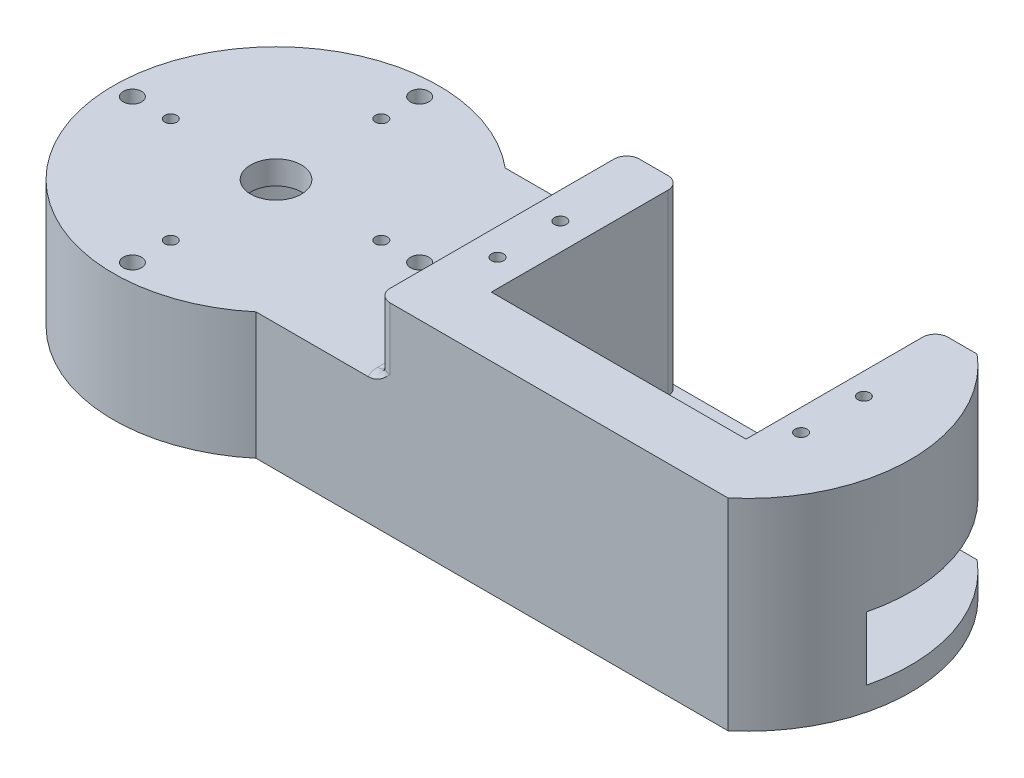
SolidWorks part; units mm, degrees
ref_plane "Front Plane" through (0, 0, 0) normal (0, 0, 1) x (1, 0, 0)
ref_plane "Top Plane" through (0, 0, 0) normal (0, 1, 0) x (1, 0, 0)
ref_plane "Right Plane" through (0, 0, 0) normal (1, 0, 0) x (0, 0, -1)
sketch "Sketch1" plane through (0, 0, 0) normal (0, 1, 0) x (1, 0, 0)
  line L0 (25.65, 0) -> (44.15, 0) construction
  line L1 (44.15, -10.195) -> (84.31, -10.195)
  line L2 (44.15, 10.195) -> (84.31, 10.195)
  line L3 (44.15, 10.195) -> (44.15, -10.195)
  line L4 (44.15, 0) -> (84.31, 0) construction
  line L5 (84.31, 10.195) -> (84.31, -10.195)
  line L6 (92.81, 17.8861) -> (92.81, -17.8861)
  line L7 (35.65, -18.695) -> (91.9869, -18.695)
  line L8 (35.65, 18.695) -> (35.65, -18.695)
  line L9 (35.65, 18.695) -> (91.9869, 18.695)
  line L10 (0, 25.65) -> (74.425, 25.65)
  line L11 (0, -25.65) -> (74.425, -25.65)
  line L12 (35.65, 18.695) -> (92.81, 18.695) construction
  line L13 (92.81, 18.695) -> (92.81, -18.695) construction
  line L14 (35.65, -18.695) -> (92.81, -18.695) construction
  circle A0 centre (0, 0) radius 15.65 construction
  circle A1 centre (16.6, 0) radius 0.95
  circle A2 centre (0, -16.6) radius 0.95
  circle A3 centre (-16.6, 0) radius 0.95
  circle A4 centre (0, 16.6) radius 0.95
  circle A5 centre (0, 0) radius 19.65
  circle A6 centre (0, 0) radius 4
  circle A7 centre (0, 0) radius 25.65
  circle A8 centre (74.425, 0) radius 25.65 construction
  arc A9 (74.425, 25.65) -> (74.425, -25.65) centre (74.425, 0) cw
  arc A10 (0, -25.65) -> (0, 25.65) centre (0, 0) cw
  point P14 (0, 0)
  point P28 (64.23, 0)
  point P29 (74.425, 0)
  dimension "D1" = 31.3
  dimension "D2" = 1.9
  dimension "D5" = 8
  dimension "D7" = 10
  dimension "D8" = 40.16
  dimension "D9" = 20.39
  dimension "D11" = 10.195
  dimension "D4" = 4
  dimension "D6" = 6
  dimension "D10" = 8.5
  dimension "D3" = 4
extrude "Boss-Extrude2" add sketch "Sketch1" along normal blind 3.7 contours A7 A5 | A5 A6 A1 A2 A3 A4 | A9 L10 A7 L11 L7 L8 L9 | A9 L9 L8 L7 L6 L2 L5 L1 L3 | L5 L2 L3 L1 | A9 L6 region at (64.23, 0, 0) region at (95.7544, 0, 0) region at (92.127, 0, 0) region at (63.8184, 0, -19.7482) region at (17.6243, 0, -17.6243) region at (-19.0942, 0, 0)
sketch "Sketch5" plane through (0, 3.7, 0) normal (0, 1, 0) x (1, 0, 0)
  line L0 (35.65, -18.695) -> (91.9869, -18.695) construction
  line L1 (35.65, 18.695) -> (35.65, -18.695) construction
  line L2 (74.425, 25.65) -> (0, 25.65)
  line L3 (0, -25.65) -> (74.425, -25.65)
  line L4 (44.15, -10.195) -> (84.31, -10.195)
  line L5 (84.31, -10.195) -> (84.31, 10.195)
  line L6 (84.31, 10.195) -> (44.15, 10.195)
  line L7 (44.15, 10.195) -> (44.15, -10.195)
  line L8 (44.15, -10.195) -> (84.31, -10.195)
  line L9 (84.31, -10.195) -> (84.31, 10.195)
  line L10 (84.31, 10.195) -> (44.15, 10.195)
  line L11 (44.15, 10.195) -> (44.15, -10.195)
  line L12 (74.425, 25.65) -> (0, 25.65)
  line L13 (0, -25.65) -> (74.425, -25.65)
  line L14 (35.65, 18.695) -> (91.9869, 18.695) construction
  line L15 (92.81, 17.8861) -> (92.81, -17.8861) construction
  line L16 (35.65, -18.695) -> (91.9869, -18.695)
  line L17 (35.65, 18.695) -> (35.65, -18.695)
  line L18 (35.65, 18.695) -> (91.9869, 18.695)
  line L19 (92.81, 17.8861) -> (92.81, -17.8861)
  circle A1 centre (0, 0) radius 4
  circle A2 centre (0, 0) radius 4
  circle A3 centre (0, 0) radius 19.65
  circle A4 centre (0, 0) radius 19.65
  circle A5 centre (0, 16.6) radius 0.95
  circle A6 centre (0, 16.6) radius 0.95
  circle A7 centre (-16.6, 0) radius 0.95
  circle A8 centre (-16.6, 0) radius 0.95
  circle A9 centre (0, -16.6) radius 0.95
  circle A10 centre (0, -16.6) radius 0.95
  circle A11 centre (16.6, 0) radius 0.95
  circle A12 centre (16.6, 0) radius 0.95
  circle A13 centre (0, 0) radius 25.65
  circle A14 centre (0, 0) radius 25.65
  arc A16 (74.425, -25.65) -> (74.425, 25.65) centre (74.425, 0) ccw
  arc A17 (0, 25.65) -> (0, -25.65) centre (0, 0) ccw
  arc A18 (74.425, -25.65) -> (74.425, 25.65) centre (74.425, 0) ccw
  arc A19 (0, 25.65) -> (0, -25.65) centre (0, 0) ccw
  arc M16 (74.425, -25.65) -> (74.425, 25.65) centre (74.425, 0) ccw
  line M17 (74.425, 25.65) -> (0, 25.65)
  arc M18 (0, 25.65) -> (0, -25.65) centre (0, 0) ccw
  line M19 (0, -25.65) -> (74.425, -25.65)
  dimension "D1" = 0
  dimension "D2" = 0
  dimension "D3" = 0
  dimension "D4" = 0
  dimension "D5" = 0
  dimension "D6" = 0
  dimension "D7" = 0
  dimension "D8" = 0
  dimension "D9" = 0
extrude "Boss-Extrude3" add sketch "Sketch5" along normal blind 28.1 contours A14 A4 M18 | L19 L18 L17 L16 L11 L10 L9 L8 M16 | A14 L16 L17 L18 M19 M16 M17 | L19 M16 region at (83.4817, 3.7, -22.8687) region at (17.6243, 3.7, -17.6243) region at (91.9243, 3.7, -17.808) region at (95.7544, 3.7, 0)
sketch "Sketch6" plane through (0, 0, -10.195) normal (0, 0, 1) x (1, 0, 0)
  line L1 (44.15, 31.8) -> (84.31, 31.8)
  line L2 (44.15, 31.8) -> (44.15, 3.7)
  line L3 (44.15, 3.7) -> (84.31, 3.7)
  line L4 (84.31, 31.8) -> (84.31, 3.7)
extrude "Cut-Extrude1" cut sketch "Sketch6" against normal up to next
sketch "Sketch7" plane through (84.31, 0, 0) normal (-1, 0, 0) x (0, 0, 1)
  line L0 (10.195, 3.7) -> (-23.6687, 3.7) construction
  line L1 (-23.6687, 3.7) -> (-23.6687, 31.8) construction
  line L2 (6.195, 3.7) -> (-23.6687, 3.7)
  line L3 (6.195, 3.7) -> (6.195, 13.7)
  line L4 (6.195, 13.7) -> (-23.6687, 13.7)
  line L5 (-23.6687, 3.7) -> (-23.6687, 13.7)
  point P0 (6.195, 3.7)
  dimension "D1" = 4
  dimension "D2" = 10
extrude "Cut-Extrude2" cut sketch "Sketch7" against normal up to next
sketch "Sketch8" plane through (0, 31.8, 0) normal (0, 1, 0) x (1, 0, 0)
  line L0 (35.65, -18.695) -> (91.9869, -18.695) construction
  line L1 (35.65, 18.695) -> (35.65, -18.695) construction
  line L2 (74.425, 25.65) -> (0, 25.65)
  line L3 (0, -25.65) -> (74.425, -25.65)
  line L4 (44.15, -10.195) -> (84.31, -10.195)
  line L5 (84.31, -10.195) -> (84.31, 10.195)
  line L6 (84.31, 10.195) -> (44.15, 10.195)
  line L7 (44.15, 10.195) -> (44.15, -10.195)
  line L8 (44.15, -10.195) -> (84.31, -10.195)
  line L9 (84.31, -10.195) -> (84.31, 10.195)
  line L10 (84.31, 10.195) -> (44.15, 10.195)
  line L11 (44.15, 10.195) -> (44.15, -10.195)
  line L12 (74.425, 25.65) -> (0, 25.65)
  line L13 (0, -25.65) -> (74.425, -25.65)
  line L14 (35.65, 18.695) -> (91.9869, 18.695) construction
  line L15 (92.81, 17.8861) -> (92.81, -17.8861) construction
  line L16 (35.65, -18.695) -> (91.9869, -18.695)
  line L17 (35.65, 18.695) -> (35.65, -18.695)
  line L18 (35.65, 18.695) -> (91.9869, 18.695)
  line L19 (92.81, 17.8861) -> (92.81, -17.8861)
  line L20 (19.65, 0) -> (25.65, 0) construction
  circle A0 centre (22.65, 0) radius 1.45
  circle A1 centre (0, 0) radius 4
  circle A2 centre (0, 0) radius 4
  circle A3 centre (0, 0) radius 19.65
  circle A4 centre (0, 0) radius 19.65
  circle A5 centre (0, 16.6) radius 0.95
  circle A6 centre (0, 16.6) radius 0.95
  circle A7 centre (-16.6, 0) radius 0.95
  circle A8 centre (-16.6, 0) radius 0.95
  circle A9 centre (0, -16.6) radius 0.95
  circle A10 centre (0, -16.6) radius 0.95
  circle A11 centre (16.6, 0) radius 0.95
  circle A12 centre (16.6, 0) radius 0.95
  circle A13 centre (0, 0) radius 25.65
  circle A14 centre (0, 0) radius 25.65
  circle A15 centre (0, -22.65) radius 1.45
  arc A16 (74.425, -25.65) -> (74.425, 25.65) centre (74.425, 0) ccw
  arc A17 (0, 25.65) -> (0, -25.65) centre (0, 0) ccw
  arc A18 (74.425, -25.65) -> (74.425, 25.65) centre (74.425, 0) ccw
  arc A19 (0, 25.65) -> (0, -25.65) centre (0, 0) ccw
  circle A20 centre (-22.65, 0) radius 1.45
  circle A21 centre (0, 22.65) radius 1.45
  point P50 (0, 0)
  dimension "D10" = 2.9
  dimension "D1" = 0
  dimension "D2" = 0
  dimension "D3" = 0
  dimension "D4" = 0
  dimension "D5" = 0
  dimension "D6" = 0
  dimension "D7" = 0
  dimension "D8" = 0
  dimension "D9" = 0
  dimension "D11" = 4
extrude "Cut-Extrude3" cut sketch "Sketch8" against normal through all both and the other way through all contours A20 | A21 | A0 | A15
sketch "Sketch9" plane through (0, 31.8, 0) normal (0, 1, 0) x (1, 0, 0)
  line L0 (35.65, -18.695) -> (91.9869, -18.695) construction
  line L1 (35.65, 18.695) -> (35.65, -18.695) construction
  line L2 (74.425, 25.65) -> (0, 25.65)
  line L3 (0, -25.65) -> (74.425, -25.65)
  line L4 (44.15, -10.195) -> (84.31, -10.195)
  line L5 (84.31, -10.195) -> (84.31, 10.195)
  line L6 (84.31, 10.195) -> (44.15, 10.195)
  line L7 (44.15, 10.195) -> (44.15, -10.195)
  line L8 (44.15, -10.195) -> (84.31, -10.195)
  line L9 (84.31, -10.195) -> (84.31, 10.195)
  line L10 (84.31, 10.195) -> (44.15, 10.195)
  line L11 (44.15, 10.195) -> (44.15, -10.195)
  line L12 (74.425, 25.65) -> (0, 25.65)
  line L13 (0, -25.65) -> (74.425, -25.65)
  line L14 (35.65, 18.695) -> (91.9869, 18.695) construction
  line L15 (92.81, 17.8861) -> (92.81, -17.8861) construction
  line L16 (35.65, -18.695) -> (91.9869, -18.695)
  line L17 (35.65, 18.695) -> (35.65, -18.695)
  line L18 (35.65, 18.695) -> (91.9869, 18.695)
  line L19 (92.81, 17.8861) -> (92.81, -17.8861)
  line L20 (35.65, 0) -> (92.81, 0) construction
  line L21 (63.8184, 18.695) -> (63.8184, -18.695) construction
  circle A0 centre (39.88, -4.95) radius 0.95
  circle A1 centre (0, 0) radius 4
  circle A2 centre (0, 0) radius 4
  circle A3 centre (0, 0) radius 19.65
  circle A4 centre (0, 0) radius 19.65
  circle A5 centre (0, 16.6) radius 0.95
  circle A6 centre (0, 16.6) radius 0.95
  circle A7 centre (-16.6, 0) radius 0.95
  circle A8 centre (-16.6, 0) radius 0.95
  circle A9 centre (0, -16.6) radius 0.95
  circle A10 centre (0, -16.6) radius 0.95
  circle A11 centre (16.6, 0) radius 0.95
  circle A12 centre (16.6, 0) radius 0.95
  circle A13 centre (0, 0) radius 25.65
  circle A14 centre (0, 0) radius 25.65
  circle A15 centre (39.88, 4.95) radius 0.95
  arc A16 (74.425, -25.65) -> (74.425, 25.65) centre (74.425, 0) ccw
  arc A17 (0, 25.65) -> (0, -25.65) centre (0, 0) ccw
  arc A18 (74.425, -25.65) -> (74.425, 25.65) centre (74.425, 0) ccw
  arc A19 (0, 25.65) -> (0, -25.65) centre (0, 0) ccw
  circle A20 centre (87.7569, -4.95) radius 0.95
  circle A21 centre (87.7569, 4.95) radius 0.95
  dimension "D10" = 1.9
  dimension "D11" = 4.27
  dimension "D12" = 4.95
  dimension "D1" = 0
  dimension "D2" = 0
  dimension "D3" = 0
  dimension "D4" = 0
  dimension "D5" = 0
  dimension "D6" = 0
  dimension "D7" = 0
  dimension "D8" = 0
  dimension "D9" = 0
extrude "Cut-Extrude4" cut sketch "Sketch9" against normal blind 12 contours A0 | A15 | A21 | A20
sketch "Sketch12" plane through (0, 31.8, 0) normal (0, 1, 0) x (1, 0, 0)
  line L0 (0, 25.65) -> (74.425, 25.65)
  line L1 (44.15, 25.65) -> (74.425, 25.65) construction
  line L2 (39.15, 19.65) -> (14.5613, 19.65) construction
  line L3 (90.9114, 19.65) -> (16.4864, 19.65)
  line L4 (-17.49, 0) -> (17.49, 0) construction
  line L5 (0, -25.65) -> (74.425, -25.65)
  line L6 (90.9114, -19.65) -> (16.4864, -19.65)
  circle A0 centre (0, 0) radius 19.65 construction
  arc A1 (0, 25.65) -> (16.4864, 19.65) centre (0, 0) cw
  arc A2 (99.3157, -6.195) -> (74.425, 25.65) centre (74.425, 0) ccw construction
  arc A3 (74.425, 25.65) -> (90.9114, 19.65) centre (74.425, 0) cw
  arc A4 (74.425, -25.65) -> (90.9114, -19.65) centre (74.425, 0) ccw
  arc A5 (0, -25.65) -> (16.4864, -19.65) centre (0, 0) ccw
extrude "Cut-Extrude5" cut sketch "Sketch12" against normal through all
fillet "Fillet1" radius 2 2 edges at (84.31, 22.75, -19.65) (44.15, 17.75, -19.65)
sketch "Sketch13" plane through (0, 31.8, 0) normal (0, 1, 0) x (1, 0, 0)
  line L0 (35.65, 19.65) -> (35.65, -19.65)
  line L1 (16.4864, 19.65) -> (42.15, 19.65) construction
  line L2 (90.9114, -19.65) -> (16.4864, -19.65) construction
  line L3 (44.15, 17.65) -> (44.15, -10.195) construction
  line L4 (35.65, 19.65) -> (16.4864, 19.65)
  line L5 (16.4864, -19.65) -> (35.65, -19.65)
  arc A0 (16.4864, 19.65) -> (16.4864, -19.65) centre (0, 0) ccw
  dimension "D1" = 8.5
extrude "Cut-Extrude6" cut sketch "Sketch13" against normal blind 11.8
sketch "Sketch14" plane through (0, 20, 0) normal (0, 1, 0) x (1, 0, 0)
  line L0 (35.65, -18.695) -> (91.9869, -18.695) construction
  line L1 (35.65, 18.695) -> (35.65, -18.695) construction
  line L2 (74.425, 25.65) -> (0, 25.65)
  line L3 (0, -25.65) -> (74.425, -25.65)
  line L4 (44.15, -10.195) -> (84.31, -10.195)
  line L5 (84.31, -10.195) -> (84.31, 10.195)
  line L6 (84.31, 10.195) -> (44.15, 10.195)
  line L7 (44.15, 10.195) -> (44.15, -10.195)
  line L8 (44.15, -10.195) -> (84.31, -10.195)
  line L9 (84.31, -10.195) -> (84.31, 10.195)
  line L10 (84.31, 10.195) -> (44.15, 10.195)
  line L11 (44.15, 10.195) -> (44.15, -10.195)
  line L12 (74.425, 25.65) -> (0, 25.65)
  line L13 (0, -25.65) -> (74.425, -25.65)
  line L14 (35.65, 18.695) -> (91.9869, 18.695) construction
  line L15 (92.81, 17.8861) -> (92.81, -17.8861) construction
  line L16 (35.65, -18.695) -> (91.9869, -18.695)
  line L17 (35.65, 18.695) -> (35.65, -18.695)
  line L18 (35.65, 18.695) -> (91.9869, 18.695)
  line L19 (92.81, 17.8861) -> (92.81, -17.8861)
  circle A0 centre (0, 0) radius 19.65
  circle A2 centre (0, 0) radius 4
  circle A3 centre (0, 0) radius 4
  circle A4 centre (0, 0) radius 19.65
  circle A5 centre (0, 0) radius 19.65
  circle A6 centre (0, 16.6) radius 0.95
  circle A7 centre (0, 16.6) radius 0.95
  circle A8 centre (-16.6, 0) radius 0.95
  circle A9 centre (-16.6, 0) radius 0.95
  circle A10 centre (0, -16.6) radius 0.95
  circle A11 centre (0, -16.6) radius 0.95
  circle A12 centre (16.6, 0) radius 0.95
  circle A13 centre (16.6, 0) radius 0.95
  circle A14 centre (0, 0) radius 25.65
  circle A15 centre (0, 0) radius 25.65
  arc A17 (74.425, -25.65) -> (74.425, 25.65) centre (74.425, 0) ccw
  arc A18 (0, 25.65) -> (0, -25.65) centre (0, 0) ccw
  arc A19 (74.425, -25.65) -> (74.425, 25.65) centre (74.425, 0) ccw
  arc A20 (0, 25.65) -> (0, -25.65) centre (0, 0) ccw
  circle M17 centre (0, 0) radius 19.65
  dimension "D1" = 0
  dimension "D2" = 0
  dimension "D3" = 0
  dimension "D4" = 0
  dimension "D5" = 0
  dimension "D6" = 0
  dimension "D7" = 0
  dimension "D8" = 0
  dimension "D9" = 0
extrude "Boss-Extrude4" add sketch "Sketch14" against normal blind 3.7 contours A13 A11 A9 A7 A3 M17 region at (-19.0942, 20, 0)
sketch "Sketch15" plane through (0, 0, 0) normal (0, -1, 0) x (1, 0, 0)
  line L0 (35.65, 18.695) -> (91.9869, 18.695) construction
  line L1 (35.65, -18.695) -> (35.65, 18.695) construction
  line L2 (0, -25.65) -> (74.425, -25.65)
  line L3 (74.425, 25.65) -> (0, 25.65)
  line L4 (84.31, 10.195) -> (44.15, 10.195)
  line L5 (84.31, -10.195) -> (84.31, 10.195)
  line L6 (44.15, -10.195) -> (84.31, -10.195)
  line L7 (44.15, 10.195) -> (44.15, -10.195)
  line L8 (84.31, 10.195) -> (44.15, 10.195)
  line L9 (84.31, -10.195) -> (84.31, 10.195)
  line L10 (44.15, -10.195) -> (84.31, -10.195)
  line L11 (44.15, 10.195) -> (44.15, -10.195)
  line L12 (0, -25.65) -> (74.425, -25.65)
  line L13 (74.425, 25.65) -> (0, 25.65)
  line L14 (35.65, -18.695) -> (91.9869, -18.695) construction
  line L15 (92.81, -17.8861) -> (92.81, 17.8861) construction
  line L16 (35.65, 18.695) -> (91.9869, 18.695)
  line L17 (35.65, -18.695) -> (35.65, 18.695)
  line L18 (35.65, -18.695) -> (91.9869, -18.695)
  line L19 (92.81, -17.8861) -> (92.81, 17.8861)
  circle A0 centre (0, 0) radius 25.65
  circle A2 centre (0, 0) radius 4
  circle A3 centre (0, 0) radius 4
  circle A4 centre (0, 0) radius 19.65
  circle A5 centre (0, 0) radius 19.65
  circle A6 centre (0, -16.6) radius 0.95
  circle A7 centre (0, -16.6) radius 0.95
  circle A8 centre (-16.6, 0) radius 0.95
  circle A9 centre (-16.6, 0) radius 0.95
  circle A10 centre (0, 16.6) radius 0.95
  circle A11 centre (0, 16.6) radius 0.95
  circle A12 centre (16.6, 0) radius 0.95
  circle A13 centre (16.6, 0) radius 0.95
  circle A14 centre (0, 0) radius 25.65
  circle A15 centre (0, 0) radius 25.65
  arc A17 (74.425, -25.65) -> (74.425, 25.65) centre (74.425, 0) ccw
  arc A18 (0, 25.65) -> (0, -25.65) centre (0, 0) ccw
  arc A19 (74.425, -25.65) -> (74.425, 25.65) centre (74.425, 0) ccw
  arc A20 (0, 25.65) -> (0, -25.65) centre (0, 0) ccw
  dimension "D1" = 0
  dimension "D2" = 0
  dimension "D3" = 0
  dimension "D4" = 0
  dimension "D5" = 0
  dimension "D6" = 0
  dimension "D7" = 0
  dimension "D8" = 0
  dimension "D9" = 0
extrude "Cut-Extrude7" cut sketch "Sketch15" against normal up to next contours A5
fillet "Fillet2" radius 2 2 edges at (35.65, 25.9, -19.65) (35.65, 25.9, 19.65)
fillet "Fillet3" radius 2 3 edges at (36.2358, 20, 19.0642) (36.2358, 20, -19.0642) (35.65, 20, 0)
